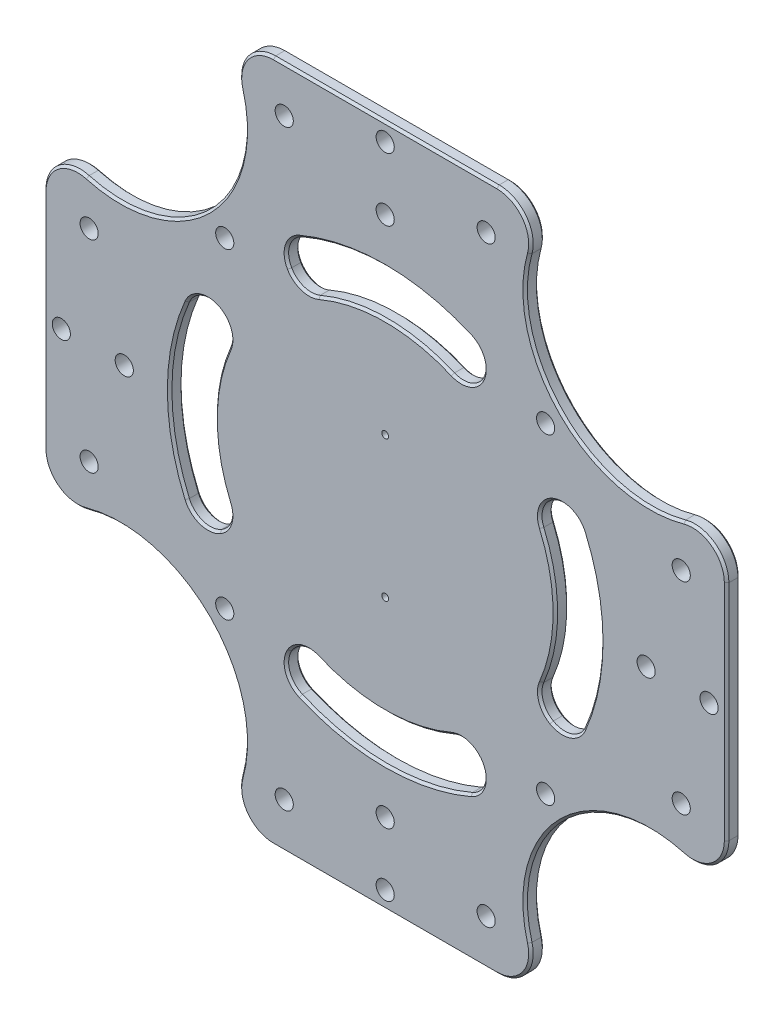
SolidWorks part; units mm, degrees
material "7075-T6 (SN)"
ref_plane "Ön Düzlem" through (0, 0, 0) normal (0, 0, 1) x (1, 0, 0)
ref_plane "Üst Düzlem" through (0, 0, 0) normal (0, 1, 0) x (1, 0, 0)
ref_plane "Sağ Düzlem" through (0, 0, 0) normal (1, 0, 0) x (0, 0, -1)
sketch "Çizim1" plane through (0, 0, 0) normal (0, 0, 1) x (1, 0, 0)
  line L0 (0, 0) -> (0, 170) construction
  line L1 (0, 0) -> (-26.0979, 198.2334) construction
  line L2 (0, 0) -> (26.0979, 198.2334) construction
  line L3 (-26.0979, 198.2334) -> (26.0979, 198.2334) construction
  line L4 (-13.256, 155.4665) -> (-29.2585, 167.4633) construction
  line L5 (29.2585, 167.4633) -> (13.256, 155.4665) construction
  line L6 (-13.256, 155.4665) -> (13.256, 155.4665) construction
  line L7 (-13.256, 155.4665) -> (13.256, 155.4665) construction
  line L8 (155.4665, 13.256) -> (167.4633, 29.2585) construction
  line L9 (155.4665, 13.256) -> (155.4665, -13.256) construction
  line L10 (167.4633, -29.2585) -> (155.4665, -13.256) construction
  line L11 (13.256, -155.4665) -> (29.2585, -167.4633) construction
  line L12 (13.256, -155.4665) -> (-13.256, -155.4665) construction
  line L13 (-29.2585, -167.4633) -> (-13.256, -155.4665) construction
  line L15 (-150.4665, 14.7843) -> (-150.4665, -14.7843) construction
  line L17 (0, 0) -> (-70.7107, 70.7107) construction
  line L18 (-150.4665, 0) -> (0, 0) construction
  line L19 (-150.4665, 42) -> (-150.4665, -42)
  line L20 (-150.4665, 42) -> (-159.565, 42)
  line L22 (-159.565, -42) -> (-150.4665, -42)
  line L23 (164.5642, 25.3851) -> (158.2141, 17.1095)
  line L24 (42, 150.4665) -> (-42, 150.4665)
  line L25 (42, 150.4665) -> (42, 159.565)
  line L26 (-42, 159.565) -> (-42, 150.4665)
  line L27 (150.4665, -42) -> (150.4665, 42)
  line L28 (150.4665, -42) -> (159.565, -42)
  line L29 (159.565, 42) -> (150.4665, 42)
  line L30 (-42, -150.4665) -> (42, -150.4665)
  line L31 (-42, -150.4665) -> (-42, -159.565)
  line L32 (42, -159.565) -> (42, -150.4665)
  arc A0 (-42, 159.565) -> (-159.565, 42) centre (0, 0) ccw
  arc A1 (-159.565, -42) -> (-42, -159.565) centre (0, 0) ccw
  arc A2 (42, -159.565) -> (159.565, -42) centre (0, 0) ccw
  arc A3 (159.565, 42) -> (42, 159.565) centre (0, 0) ccw
  circle A4 centre (0, 0) radius 90 construction
  circle A5 centre (0, 115) radius 4
  circle A6 centre (115, 0) radius 4
  circle A7 centre (0, -115) radius 4
  circle A8 centre (-115, 0) radius 4
  circle A9 centre (-70.7107, 70.7107) radius 4
  circle A10 centre (70.7107, 70.7107) radius 4
  circle A11 centre (70.7107, -70.7107) radius 4
  circle A12 centre (-70.7107, -70.7107) radius 4
  point P1 (0, 115)
  point P8 (-21.2573, 161.4649)
  point P12 (21.2573, 161.4649)
  point P25 (0, 90)
  point P45 (-150.4665, 0)
  point P65 (21.2473, 161.3892)
  dimension "D1" = 330
  dimension "D4" = 180
  dimension "D5" = 8
  dimension "D9" = 8
  dimension "D11" = 84
  dimension "D2" = 7.5
  dimension "D3" = 20
  dimension "D6" = 115
  dimension "D7" = 150.4665
  dimension "D8" = 45
  dimension "D10" = 100
  dimension "D12" = 4
extrude "Yükseklik-Ekstrüzyon1" add sketch "Çizim1" along normal blind 6 contours L29 A3 L25 L24 L26 A0 L20 L19 L22 A1 L31 L30 L32 A2 L28 L27 A12 A11 A10 A9 A8 A7 A6 A5 A4
fillet "Radyus1" radius 5 8 edges at (42, -159.565, 3) (-42, -159.565, 3) (-159.565, -42, 3) (-159.565, 42, 3) (-42, 159.565, 3) (42, 159.565, 3) (159.565, 42, 3) (159.565, -42, 3)
sketch "Çizim2" plane through (0, 0, 6) normal (0, 0, 1) x (1, 0, 0)
  line L0 (0, 0) -> (-147.7332, -0.0007) construction
  line L1 (0, 0) -> (-135.4665, 44.4956) construction
  line L2 (0, 0) -> (-135.4665, -44.4969) construction
  circle A0 centre (-130.4665, -44.4969) radius 4
  circle A1 centre (-142.7332, -0.0007) radius 4
  circle A2 centre (-130.4665, 44.4956) radius 4
  dimension "D1" = 137.8454
  dimension "D2" = 142.7332
  dimension "D3" = 137.8459
extrude "Kes-Ekstrüzyon1" cut sketch "Çizim2" against normal blind 10
pattern_circular "Dairesel Kaplama1" count 4 over 360 about axis through (0, 0, 0) along (0, 0, 1) of "Kes-Ekstrüzyon1"
sketch "Sketch1" plane through (0, 0, 0) normal (0, 0, -1) x (-1, 0, 0)
  line L1 (-85.3028, 176.3035) -> (85.3028, 176.3035)
  line L2 (-85.3028, 176.3035) -> (-85.3028, 150.4665)
  line L3 (-85.3028, 150.4665) -> (85.3028, 150.4665)
  line L4 (85.3028, 176.3035) -> (85.3028, 150.4665)
  line L5 (-85.3028, 176.3035) -> (85.3028, 150.4665) construction
  line L6 (-85.3028, 150.4665) -> (85.3028, 176.3035) construction
  point P0 (0, 163.385)
extrude "Cut-Extrude1" cut sketch "Sketch1" against normal blind 10
pattern_circular "CirPattern1" count 4 over 360 about axis through (0, 0, 0) along (0, 0, 1) of "Cut-Extrude1"
fillet "Fillet1" radius 50 8 edges at (-67.7114, 150.4665, 3) (67.7114, 150.4665, 3) (150.4665, 67.7114, 3) (150.4665, -67.7114, 3) (67.7114, -150.4665, 3) (-67.7114, -150.4665, 3) (-150.4665, -67.7114, 3) (-150.4665, 67.7114, 3)
sketch "Sketch2" plane through (0, 0, 0) normal (0, 0, -1) x (-1, 0, 0)
  line L0 (-150.4665, -55.9597) -> (-150.4665, 55.9597) construction
  line L1 (-116.6726, 116.6726) -> (-77.7817, 77.7817) construction
  line L3 (-49.2427, 150.4665) -> (-49.2427, 163.8481)
  line L4 (-49.2427, 163.8481) -> (-162.9006, 163.8481)
  line L5 (-162.9006, 163.8481) -> (-162.9006, 49.2427)
  line L6 (-162.9006, 49.2427) -> (-150.4665, 49.2427)
  arc A0 (-131.4392, 63.692) -> (-63.692, 131.4392) centre (-116.6726, 116.6726) ccw
  arc A1 (-80.29, 144.1476) -> (-144.1476, 80.29) centre (0, 0) ccw construction
  arc A2 (-131.4392, 63.692) -> (-150.4665, 49.2427) centre (-135.4665, 49.2427) ccw
  arc A3 (-63.692, 131.4392) -> (-49.2427, 150.4665) centre (-49.2427, 135.4665) cw
  dimension "D1" = 110
  dimension "D2" = 30
extrude "Cut-Extrude2" cut sketch "Sketch2" against normal blind 10
sketch "Sketch3" plane through (0, 0, 0) normal (0, 0, -1) x (-1, 0, 0)
  line L0 (0, 0) -> (-95, 0) construction
  line L1 (-64.9519, 37.5) -> (-82.2724, 47.5)
  line L2 (-64.9519, -37.5) -> (-82.2724, -47.5)
  circle A0 centre (-115, 0) radius 12 construction
  arc A4 (-64.9519, 37.5) -> (-64.9519, -37.5) centre (0, 0) ccw
  arc A5 (-82.2724, 47.5) -> (-82.2724, -47.5) centre (0, 0) ccw
  dimension "D1" = 24
  dimension "D2" = 190
  dimension "D3" = 150
  dimension "D4" = 30
extrude "Cut-Extrude3" cut sketch "Sketch3" against normal blind 10
fillet "Fillet2" radius 10 4 edges at (82.2724, -47.5, 3) (64.9519, -37.5, 3) (64.9519, 37.5, 3) (82.2724, 47.5, 3)
pattern_circular "CirPattern3" count 4 over 360 about axis through (0, 0, 0) along (0, 0, 1) of "Cut-Extrude3", "Fillet2"
pattern_circular "CirPattern2" count 4 over 360 about axis through (0, 0, 0) along (0, 0, 1) of "Cut-Extrude2"
chamfer "Chamfer1" distance 1 angle 45 80 edges at (0, 75, 6) (36.6975, 68.611, 6) (-36.6975, 68.611, 6) (43.0346, 81.2538, 6) (-43.0346, 81.2538, 6) (0, 95, 6) (0, 75, 0) (-36.6975, 68.611, 0) (36.6975, 68.611, 0) (-43.0346, 81.2538, 0) (43.0346, 81.2538, 0) (0, 95, 0) (-75, 0, 6) (-68.611, 36.6975, 6) (-68.611, -36.6975, 6) (-81.2538, 43.0346, 6) (-81.2538, -43.0346, 6) (-95, 0, 6) (-75, 0, 0) (-68.611, -36.6975, 0) (-68.611, 36.6975, 0) (-81.2538, -43.0346, 0) (-81.2538, 43.0346, 0) (-95, 0, 0) (0, -95, 6) (43.0346, -81.2538, 6) (-43.0346, -81.2538, 6) (36.6975, -68.611, 6) (-36.6975, -68.611, 6) (0, -75, 6) (0, -95, 0) (-43.0346, -81.2538, 0) (43.0346, -81.2538, 0) (-36.6975, -68.611, 0) (36.6975, -68.611, 0) (0, -75, 0) (95, 0, 6) (81.2538, 43.0346, 6) (81.2538, -43.0346, 6) (68.611, 36.6975, 6) (68.611, -36.6975, 6) (75, 0, 6) (95, 0, 0) (81.2538, -43.0346, 0) (81.2538, 43.0346, 0) (68.611, -36.6975, 0) (68.611, 36.6975, 0) (75, 0, 0) (-150.4665, 0, 6) (-144.5382, -61.1886, 6) (-144.5382, 61.1886, 6) (-77.7817, -77.7817, 6) (-77.7817, 77.7817, 6) (-61.1886, -144.5382, 6) (-61.1886, 144.5382, 6) (0, -150.4665, 6) (0, 150.4665, 6) (61.1886, -144.5382, 6) (61.1886, 144.5382, 6) (77.7817, -77.7817, 6) (77.7817, 77.7817, 6) (144.5382, -61.1886, 6) (144.5382, 61.1886, 6) (150.4665, 0, 6) (-77.7817, -77.7817, 0) (-61.1886, -144.5382, 0) (-144.5382, -61.1886, 0) (0, -150.4665, 0) (-150.4665, 0, 0) (61.1886, -144.5382, 0) (-144.5382, 61.1886, 0) (77.7817, -77.7817, 0) (-77.7817, 77.7817, 0) (144.5382, -61.1886, 0) (-61.1886, 144.5382, 0) (150.4665, 0, 0) (0, 150.4665, 0) (144.5382, 61.1886, 0) (61.1886, 144.5382, 0) (77.7817, 77.7817, 0)
sketch "Sketch4" plane through (0, 0, 6) normal (0, 0, 1) x (1, 0, 0)
  line L0 (0, 31) -> (0, -31) construction
  circle A0 centre (0, 31) radius 1.5
  circle A1 centre (0, -31) radius 1.5
  point P3 (0, 0)
  dimension "D2" = 3
  dimension "D3" = 3
  dimension "D1" = 62
extrude "Cut-Extrude4" cut sketch "Sketch4" against normal blind 10 contours A0 | A1
